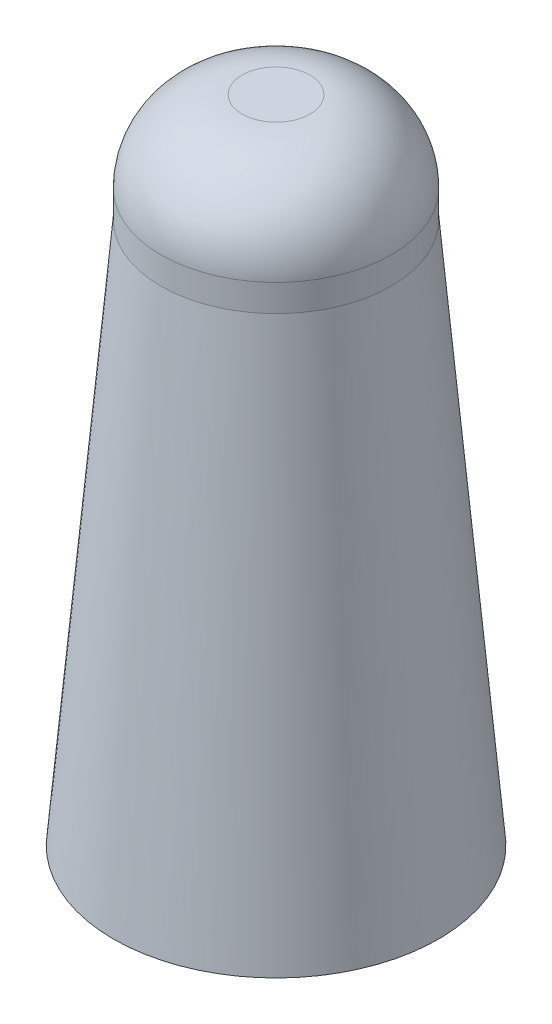
SolidWorks part; units mm, degrees
ref_plane "Front Plane" through (0, 0, 0) normal (0, 0, 1) x (1, 0, 0)
ref_plane "Top Plane" through (0, 0, 0) normal (0, 1, 0) x (1, 0, 0)
ref_plane "Right Plane" through (0, 0, 0) normal (1, 0, 0) x (0, 0, -1)
sketch "Sketch1" plane through (0, 0, 0) normal (0, 1, 0) x (1, 0, 0)
  circle A0 centre (0, 0) radius 6
  dimension "D1" = 12
extrude "Boss-Extrude1" add sketch "Sketch1" along normal blind 20
chamfer "Chamfer4" distance 20 angle 5 1 edges at (0, 20, 6) first distance on face at (0, 20, 6)
sketch "Sketch2" plane through (0, 0, 0) normal (0, -1, 0) x (-1, 0, 0)
  circle A0 centre (0, 0) radius 3.35
  dimension "D1" = 6.7
extrude "Cut-Extrude1" cut sketch "Sketch2" against normal blind 18
thread "Thread1" pitch 0.7056 method cut profile "Thread Profile1" start angle 45, offset 0.5, length 17.6, pitch 0.7056, diameter 6.7
ref_plane "Plane1" through (-2.3688, 17.5, -2.3688) normal (-0.7071, 0, 0.7071) x (-0.7071, 0, -0.7071)
sketch "Thread Profile1" plane through (-2.3688, 17.5, -2.3688) normal (-0.7071, 0, 0.7071) x (-0.7071, 0, -0.7071)
  line L0 (0, 0) -> (0, 0.7056) construction
  line L1 (0, 0) -> (0.3819, 0.2205)
  line L2 (0.3819, 0.2205) -> (0.3819, 0.3087)
  line L3 (0.3819, 0.3087) -> (0, 0.5292)
  line L4 (0.3819, 0.2646) -> (0, 0.2646) construction
  line L11 (0, 0) -> (0, 0.5292)
  point P2 (0, 0)
  dimension "Pitch" = 0.7056
  dimension "Profile_Angle" = 60
  dimension "Profile_Land" = 0.0882
  dimension "Profile_Height" = 0.3819
sketch "Sketch10" plane through (0, 20, 0) normal (0, 1, 0) x (1, 0, 0)
  circle A0 centre (0, 0) radius 4.2502
extrude "Boss-Extrude2" add sketch "Sketch10" along normal blind 4
fillet "Fillet5" radius 3 1 edges at (0, 24, 4.2502)
